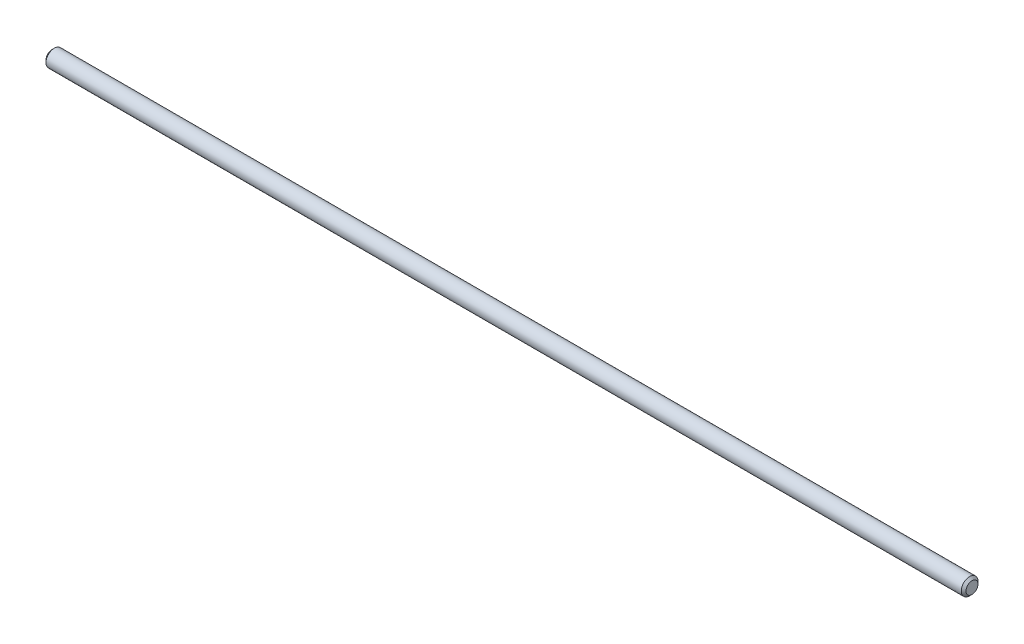
SolidWorks part; units mm, degrees
ref_plane "Front Plane" through (0, 0, 0) normal (0, 0, 1) x (1, 0, 0)
ref_plane "Top Plane" through (0, 0, 0) normal (0, 1, 0) x (1, 0, 0)
ref_plane "Right Plane" through (0, 0, 0) normal (1, 0, 0) x (0, 0, -1)
sketch "Sketch1" plane through (0, 0, 0) normal (0, 0, 1) x (1, 0, 0)
  line L0 (-114.3, 0) -> (114.3, 0) construction
  line L1 (114.3, 2.0828) -> (114.3, -2.0828) construction
  line L2 (-114.3, 2.0828) -> (-114.3, -2.0828) construction
  point P6 (111.5219, -2.0828)
  dimension "Thread Diameter" = 4.1656
  dimension "Length" = 228.6
  dimension "D1" = 2.7781
sketch "Sketch2" plane through (0, 0, 0) normal (1, 0, 0) x (0, 0, -1)
  circle A0 centre (0, 0) radius 2.0828
extrude "Boss-Extrude1" add sketch "Sketch2" against normal up to vertex (114.3 mm away) and the other way up to vertex (114.3 mm away) up to point (-114.3, 0, 0) other way up to point (114.3, 0, 0)
sketch "Sketch3" plane through (114.3, 0, 0) normal (1, 0, 0) x (0, 0, -1)
  circle A1 centre (0, 0) radius 2.0828
  circle A2 centre (0, 0) radius 2.0828
  dimension "D1" = 0
curve "Helix/Spiral1" pitch 0.7937 height 229.3937 turns 289 parameters "Pitch"=0.7937
chamfer "Chamfer1" distance 0.5953 angle 45 2 edges at (-114.3, 0, -2.0828) (114.3, 0, -2.0828)
sketch "Sketch4" plane through (0, 0, 0) normal (0, 0, 1) x (1, 0, 0)
  line L0 (114.2504, 2.1687) -> (114.6473, 1.4813) construction
  line L1 (114.6473, 1.4813) -> (115.0441, 2.1687) construction
  line L2 (115.0441, 2.1687) -> (114.2504, 2.1687) construction
  line L3 (114.6473, 2.1687) -> (114.6473, 2.0828) construction
  line L4 (114.6473, 1.4813) -> (114.6473, 1.5672) construction
  line L5 (114.5977, 1.5672) -> (114.6969, 1.5672) construction
  line L6 (114.3, 2.0828) -> (114.9945, 2.0828) construction
  line L7 (114.5977, 1.5672) -> (114.2752, 2.1258)
  line L8 (114.5977, 1.5672) -> (114.6969, 1.5672)
  line L9 (114.2752, 2.1258) -> (115.0193, 2.1258)
  line L10 (115.0193, 2.1258) -> (114.6969, 1.5672)
  point P13 (114.6473, 2.1258)
  dimension "D2" = 0.0992
sweep "Cut-Sweep3" [suppressed] cut profiles "Sketch4" path "Helix/Spiral1"
equation "\"D3@Helix/Spiral1\" = \"Length@Sketch1\"+\"Pitch@Helix/Spiral1\""
equation "\"D1@Chamfer1\" = \"Pitch@Helix/Spiral1\"*.75"
equation "\"D1@Sketch4\" = \"Pitch@Helix/Spiral1\""
equation "\"D2@Sketch4\" = \"D1@Sketch4\"/8"
equation "\"D1@Sketch1\" = \"Pitch@Helix/Spiral1\"*3.50"
